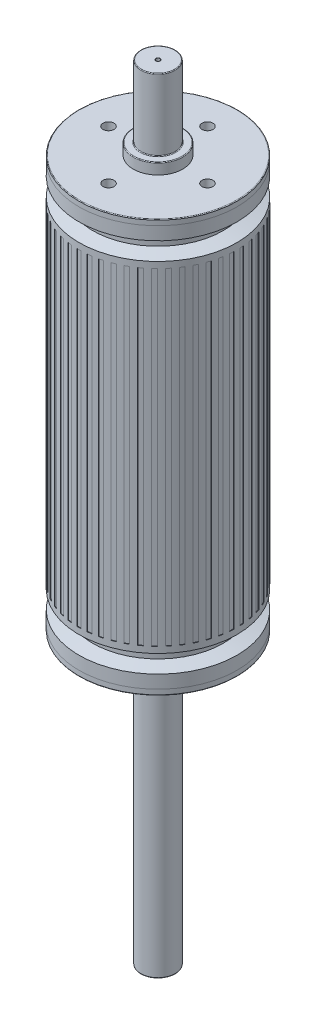
SolidWorks part; units mm, degrees
ref_plane "Ön Düzlem" through (0, 0, 0) normal (0, 0, 1) x (1, 0, 0)
ref_plane "Üst Düzlem" through (0, 0, 0) normal (0, 1, 0) x (1, 0, 0)
ref_plane "Sağ Düzlem" through (0, 0, 0) normal (1, 0, 0) x (0, 0, -1)
sketch "Sketch1" plane through (0, 0, 0) normal (0, 0, 1) x (1, 0, 0)
  line L0 (0, 0) -> (0, 390)
  line L1 (0, 0) -> (12.5, 0) construction
  line L2 (12.5, 0) -> (12.5, 22)
  line L3 (18, 30) -> (57.5, 30)
  line L4 (57.5, 30) -> (57.5, 330)
  line L5 (57.5, 330) -> (18, 330)
  line L6 (12.5, 390) -> (12.5, 338)
  line L7 (0, 390) -> (12.5, 390)
  line L8 (12.5, 22) -> (18, 22)
  line L9 (18, 22) -> (18, 30)
  line L10 (12.5, 338) -> (18, 338)
  line L11 (18, 338) -> (18, 330)
  line L12 (0, 180) -> (57.5, 180) construction
  line L13 (47.5, 54) -> (57.5, 56.5)
  line L14 (47.5, 54) -> (47.5, 46)
  line L15 (47.5, 46) -> (57.5, 43.5)
  line L16 (47.5, 50) -> (57.5, 50) construction
  line L17 (47.5, 54) -> (57.5, 56.5)
  line L18 (47.5, 46) -> (57.5, 43.5)
  line L19 (47.5, 310) -> (57.5, 310) construction
  line L20 (47.5, 314) -> (57.5, 316.5)
  line L21 (47.5, 306) -> (57.5, 303.5)
  line L22 (47.5, 314) -> (57.5, 316.5)
  line L23 (47.5, 306) -> (57.5, 303.5)
  line L24 (47.5, 306) -> (47.5, 314)
  line L25 (0, 0) -> (0, -180)
  line L26 (0, -180) -> (12.5, -180)
  line L27 (12.5, -180) -> (12.5, 0)
  dimension "D1" = 12.5
  dimension "D2" = 30
  dimension "D3" = 18
  dimension "D4" = 8
  dimension "D5" = 300
  dimension "D6" = 57.5
  dimension "D7" = 8
  dimension "D8" = 13
  dimension "D9" = 10
  dimension "D10" = 20
  dimension "D11" = 60
  dimension "D12" = 510
revolve "Revolve1" add sketch "Sketch1" angle 360 about L0 region at (24.741, 153.9367, 0)
ref_axis "Axis1" through (0, 303.5, 0) along (0, -1, 0)
ref_plane "Plane1" through (0, 54, 0) normal (0, 1, 0) x (1, 0, 0)
ref_plane "Plane2" through (0, 306, 0) normal (0, -1, 0) x (-1, 0, 0)
ref_plane "Plane3" through (0, 61, 0) normal (0, 1, 0) x (1, 0, 0)
ref_plane "Plane4" through (0, 299, 0) normal (0, -1, 0) x (-1, 0, 0)
sketch "Sketch3" plane through (0, 61, 0) normal (0, 1, 0) x (1, 0, 0)
  line L1 (1.5, 57.1) -> (-1.5, 57.1)
  line L2 (1.5, 57.1) -> (1.5, 57.9)
  line L3 (1.5, 57.9) -> (-1.5, 57.9)
  line L4 (-1.5, 57.1) -> (-1.5, 57.9)
  line L5 (1.5, 57.1) -> (-1.5, 57.9) construction
  line L6 (1.5, 57.9) -> (-1.5, 57.1) construction
  circle A0 centre (0, 0) radius 57.5 construction
  point P0 (0, 57.5)
  dimension "D1" = 3
  dimension "D2" = 0.8
extrude "Cut-Extrude2" cut sketch "Sketch3" along normal up to surface (238 mm away) up to plane "Plane4"
pattern_circular "CirPattern1" count 50 over 360 of "Cut-Extrude2"
ref_plane "Plane5" through (0, 180, 0) normal (0, 1, 0) x (1, 0, 0)
sketch "Sketch4" plane through (0, 30, 0) normal (0, -1, 0) x (1, 0, 0)
  circle A0 centre (0, 36) radius 4
  circle A1 centre (36, 0) radius 4
  circle A2 centre (0, -36) radius 4
  circle A3 centre (-36, 0) radius 4
  point P12 (0, 0)
  dimension "D1" = 8
  dimension "D2" = 36
  dimension "D3" = 4
extrude "Cut-Extrude3" cut sketch "Sketch4" against normal blind 50
ref_plane "Plane6" through (0, 34, 0) normal (0, -1, 0) x (-1, 0, 0)
ref_plane "Plane7" through (0, 326, 0) normal (0, 1, 0) x (1, 0, 0)
split line "Split Line1"
split line "Split Line2"
fillet "Fillet1" radius 0.5 9 edges at (18, 338, 0) (57.5, 30, 0) (57.5, 330, 0) (12.5, 338, 0) (18, 30, 0) (18, 22, 0) (12.5, 22, 0) (12.5, -180, 0) (12.5, 390, 0)
mirror "Mirror1" about plane through (0, 180, 0) normal (0, 1, 0) of "Cut-Extrude3"
sketch "Sketch5" plane through (0, 390, 0) normal (0, 1, 0) x (1, 0, 0)
  circle A0 centre (0, 0) radius 1.5
  dimension "D1" = 3
extrude "Cut-Extrude4" cut sketch "Sketch5" against normal blind 4
sketch "Sketch6" plane through (0, -180, 0) normal (0, -1, 0) x (1, 0, 0)
  circle A0 centre (0, 0) radius 2
  dimension "D1" = 4
extrude "Cut-Extrude5" cut sketch "Sketch6" against normal blind 4
fillet "Fillet2" radius 1 2 edges at (-1.5, 386, 0) (2, -176, 0)
fillet "Fillet3" radius 0.1 2 edges at (2, -180, 0) (-1.5, 390, 0)
